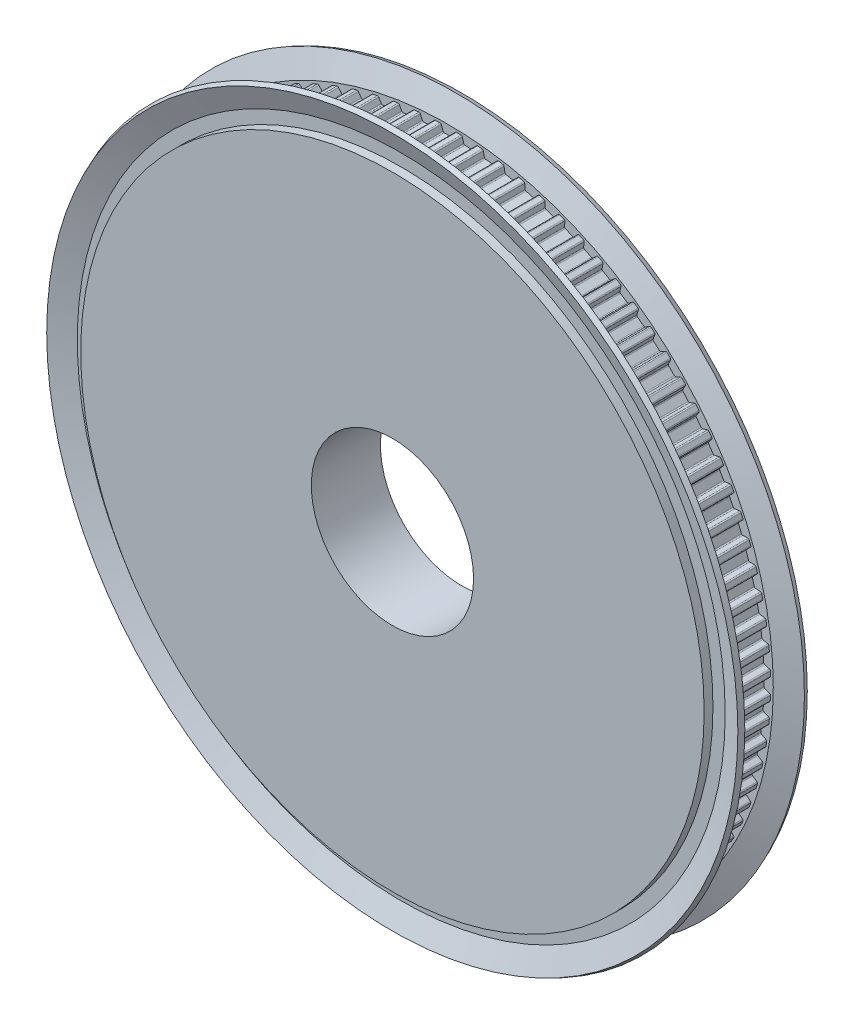
SolidWorks part; units mm, degrees
ref_plane "Front Plane" through (0, 0, 0) normal (0, 0, 1) x (1, 0, 0)
ref_plane "Top Plane" through (0, 0, 0) normal (0, 1, 0) x (1, 0, 0)
ref_plane "Right Plane" through (0, 0, 0) normal (1, 0, 0) x (0, 0, -1)
ref_axis "Axis1" through (0, 0, 55) along (0, 0, -1)
sketch "SketchRevolveGearBelt01" plane through (0, 0, 0) normal (1, 0, 0) x (0, 0, -1)
  line L0 (0, 0) -> (1, 0) construction
  line L1 (3.302, 0) -> (3.302, 29.7767)
  line L2 (3.302, 29.7767) -> (2.4606, 29.7767)
  line L3 (2.4606, 29.7767) -> (2.4606, 30.9456)
  line L4 (2.4606, 30.9456) -> (3.3162, 33.0113)
  line L5 (3.3162, 33.0113) -> (2.8469, 33.2057)
  line L6 (2.8469, 33.2057) -> (2.032, 31.0467)
  line L7 (2.032, 31.0467) -> (2.032, 30.7967)
  line L8 (2.032, 30.7967) -> (-2.032, 30.7967)
  line L9 (-2.032, 30.7967) -> (-2.032, 31.0467)
  line L10 (-2.032, 31.0467) -> (-2.8469, 33.2057)
  line L11 (-2.8469, 33.2057) -> (-3.3162, 33.0113)
  line L12 (-3.3162, 33.0113) -> (-2.4606, 30.9456)
  line L13 (-2.4606, 30.9456) -> (-2.4606, 29.7767)
  line L14 (-2.4606, 29.7767) -> (-3.302, 29.7767)
  line L15 (-3.302, 29.7767) -> (-3.302, 0)
  line L16 (-3.302, 0) -> (3.302, 0)
  dimension "GearBeltSide1" = 3.302
  dimension "GearBeltFlange1OutsideWidth" = 2.4606
  dimension "GearBeltFlange1OutsideLength" = 1.169
  dimension "GearBeltFlange1X" = 0.8556
  dimension "GearBeltFlange1Y" = 2.0656
  dimension "GearBeltFlangeThickness" = 1.821
  dimension "GearBeltToothWidth1" = 2.032
  dimension "GearBeltFlangeInside" = 0.25
  dimension "GearBeltOutsideDiameter" = 30.7967
  dimension "GearBeltToothWidth2" = 2.032
  dimension "GearBeltFlange2X" = 0.8556
  dimension "GearBeltFlange2OutsideWidth" = 2.4606
revolve "GearBelt01" add sketch "SketchRevolveGearBelt01" angle 360 about L0
sketch "SketchToothGearBelt01" plane through (0, 0, 0) normal (0, 0, 1) x (1, 0, 0)
  line L0 (-0.6657, 30.7031) -> (-0.499, 30.2452)
  line L1 (-0.3797, 30.1617) -> (0.3797, 30.1617)
  line L2 (0.499, 30.2452) -> (0.6657, 30.7031)
  line L3 (0.7883, 30.7866) -> (0, 33.3266)
  line L4 (0, 33.3266) -> (-0.7883, 30.7866)
  arc A0 (-0.7883, 30.7866) -> (-0.6657, 30.7031) centre (-0.785, 30.6596) cw
  arc A1 (-0.499, 30.2452) -> (-0.3797, 30.1617) centre (-0.3797, 30.2887) ccw
  arc A2 (0.3797, 30.1617) -> (0.499, 30.2452) centre (0.3797, 30.2887) ccw
  arc A3 (0.6657, 30.7031) -> (0.7883, 30.7866) centre (0.785, 30.6596) cw
  dimension "GearBeltToothR1" = 0.254
  dimension "GearBeltToothR2" = 0.254
  dimension "GearBeltToothX1" = 0.1666
  dimension "GearBeltToothY1" = 0.4578
  dimension "GearBeltToothRootX" = 30.1617
  dimension "GearBeltToothRootY" = 30.1617
  dimension "GearBeltToothX2" = 0.1666
  dimension "GearBeltToothY2" = 0.4578
  dimension "GearBeltToothCapX1" = 0.7883
  dimension "GearBeltToothCapY1" = 2.54
  dimension "GearBeltToothCapX2" = 0.7883
  dimension "GearBeltToothCapY2" = 2.54
extrude "ToothExtrudeCutGearBelt01" cut sketch "SketchToothGearBelt01" against normal blind 2.032 and the other way blind 2.032
pattern_circular "PatternGearBelt01" count 96 every 3.75 about axis through (0, 0, 55) along (0, 0, -1) of "ToothExtrudeCutGearBelt01"
sketch "BoreRevolveSketch" plane through (0, 0, 0) normal (1, 0, 0) x (0, 0, -1)
  line L0 (0, 0) -> (1, 0) construction
  line L1 (-3.302, 0) -> (3.302, 0)
  line L2 (3.302, 0) -> (3.302, 7.75)
  line L3 (3.302, 7.75) -> (-3.302, 7.75)
  line L4 (-3.302, 7.75) -> (-3.302, 0)
  dimension "BoreSide1" = 3.302
  dimension "TaperSide1" = 7.75
  dimension "BoreSide2" = 3.302
  dimension "TaperSide2" = 7.75
revolve "BoreRevolveCut" cut sketch "BoreRevolveSketch" angle 360 about L0
sketch "AuxiliarySketchGearBelt01" plane through (0, 0, 0) normal (0, 0, 1) x (1, 0, 0)
  circle A0 centre (0, 0) radius 31.0467 construction
  dimension "PitchDiameter" = 62.0933
